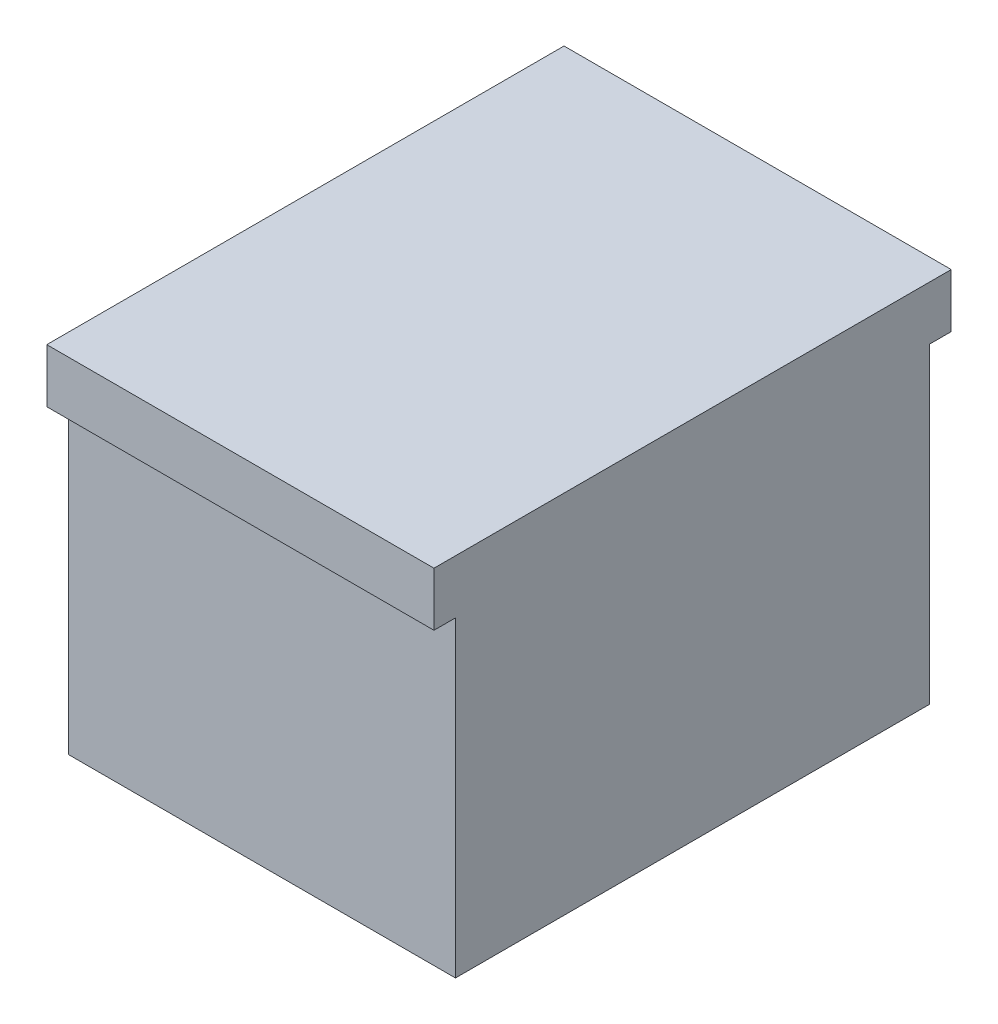
SolidWorks part; units mm, degrees
material "leadbattery"
ref_plane "Front" through (0, 0, 0) normal (0, 0, 1) x (1, 0, 0)
ref_plane "Top" through (0, 0, 0) normal (0, 1, 0) x (1, 0, 0)
ref_plane "Right" through (0, 0, 0) normal (1, 0, 0) x (0, 0, -1)
sketch "Sketch1" plane through (0, 0, 0) normal (0, 1, 0) x (1, 0, 0)
  line L1 (114.3, 140) -> (-114.3, 140)
  line L2 (114.3, 140) -> (114.3, -140)
  line L3 (114.3, -140) -> (-114.3, -140)
  line L4 (-114.3, 140) -> (-114.3, -140)
  line L5 (114.3, 140) -> (-114.3, -140) construction
  line L6 (114.3, -140) -> (-114.3, 140) construction
  point P0 (0, 0)
  dimension "D1" = 228.6
  dimension "D2" = 280
extrude "Boss-Extrude1" add sketch "Sketch1" along normal blind 215.9
hole_wizard "M5 Clearance Hole1" positions "Sketch2" profile "Sketch3" hole size "M5" standard "ANSI Metric"
sketch "Sketch2" plane through (0, 0, 0) normal (0, -1, 0) x (-1, 0, 0)
  line L2 (-114.3, -140) -> (-114.3, 140) construction
  line L3 (57.6835, 75.946) -> (57.6835, -75.946)
  line L4 (57.6835, -75.946) -> (-76.2, 0)
  line L5 (-76.2, 0) -> (57.6835, 75.946)
  line L6 (-114.3, -140) -> (-76.2, 0) construction
  line L8 (-114.3, 140) -> (-76.2, 0) construction
  point P0 (-76.2, 0)
  point P19 (57.6835, 75.946)
  point P21 (57.6835, -75.946)
  dimension "D2" = 38.1
  dimension "D3" = 151.892
  dimension "D4" = 153.924
  dimension "D5" = 153.924
sketch "Sketch3" plane through (76.2, 0, 0) normal (1, 0, 0) x (0, 0, -1)
  line L0 (0, 0) -> (0, 41.6524)
  line L1 (0, 41.6524) -> (2.75, 40)
  line L2 (2.75, 40) -> (2.75, 0)
  line L5 (2.75, 0) -> (0, 0)
  line L10 (0, 41.6524) -> (-2.75, 40) construction
  line L11 (0, -6.35) -> (0, 107.95) construction
  dimension "Hole Dia." = 5.5
  dimension "Hole Depth" = 40
  dimension "Drill Angle" = 118
sketch "Sketch4" plane through (0, 0, 0) normal (0, -1, 0) x (1, 0, 0)
  circle A0 centre (-57.6835, -75.946) radius 7.3787
  circle A1 centre (-57.6835, -75.946) radius 2.75 construction
  circle A2 centre (-57.6835, -75.946) radius 2.75
  circle A3 centre (-57.6835, 75.946) radius 7.3787
  circle A4 centre (-57.6835, 75.946) radius 2.75 construction
  circle A5 centre (-57.6835, 75.946) radius 2.75
  dimension "D1" = 14.7574
extrude "Boss-Extrude2" add sketch "Sketch4" along normal blind 10.5918
sketch "Sketch5" plane through (0, 215.9, 0) normal (0, 1, 0) x (1, 0, 0)
  line L0 (-114.3, 140) -> (-114.3, -140) construction
  line L1 (114.3, -152.7) -> (-114.3, -152.7)
  line L2 (114.3, -152.7) -> (114.3, 152.7)
  line L3 (114.3, 152.7) -> (-114.3, 152.7)
  line L4 (-114.3, -152.7) -> (-114.3, 152.7)
  line L5 (114.3, -152.7) -> (-114.3, 152.7) construction
  line L6 (114.3, 152.7) -> (-114.3, -152.7) construction
  line L7 (114.3, 140) -> (-114.3, 140) construction
  point P0 (0, 0)
  dimension "D1" = 12.7
extrude "Boss-Extrude3" add sketch "Sketch5" against normal blind 31.75
ref_axis "Axis1" through (-57.6835, -10.5918, 75.946) along (0, 1, 0)
ref_axis "Axis2" through (-57.6835, -10.5918, -75.946) along (0, 1, 0)
ref_plane "Plane1" through (-57.6835, 0, 0) normal (-1, 0, 0) x (0, 0, 1)
